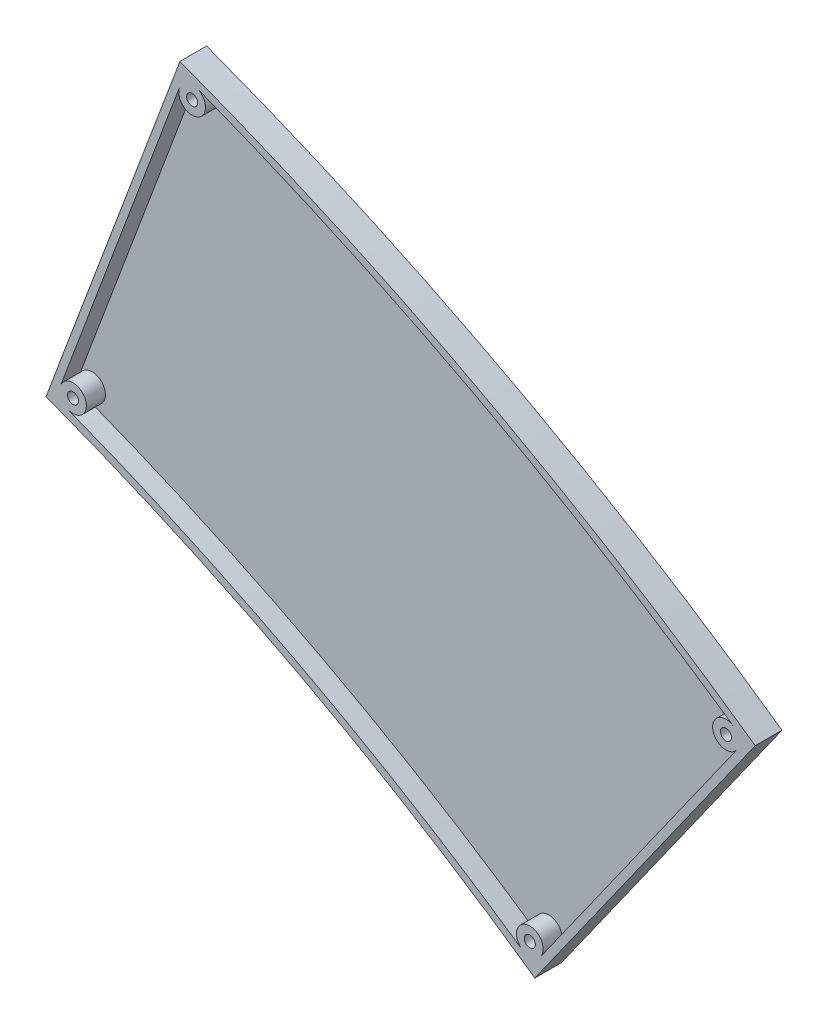
SolidWorks part; units mm, degrees
ref_plane "Front Plane" through (0, 0, 0) normal (0, 0, 1) x (1, 0, 0)
ref_plane "Top Plane" through (0, 0, 0) normal (0, 1, 0) x (1, 0, 0)
ref_plane "Right Plane" through (0, 0, 0) normal (1, 0, 0) x (0, 0, -1)
sketch "Sketch2" plane through (0, 0, 0) normal (0, 0, 1) x (1, 0, 0)
  line L0 (0, 0) -> (198.2974, 529.0587) construction
  line L1 (0, 0) -> (326.4209, 461.1664) construction
  line L2 (198.2974, 529.0587) -> (233.3943, 622.6975)
  line L3 (326.4209, 461.1664) -> (384.1945, 542.7887)
  arc A1 (326.4209, 461.1664) -> (198.2974, 529.0587) centre (0, 0) ccw
  arc A2 (384.1945, 542.7887) -> (233.3943, 622.6975) centre (0, 0) ccw
  dimension "D1" = 1330
  dimension "D2" = 100
  dimension "D3" = 145
extrude "Boss-Extrude1" add sketch "Sketch2" against normal blind 2
sketch "Sketch4" plane through (0, 0, 0) normal (0, 0, 1) x (1, 0, 0)
  line L0 (233.3943, 622.6975) -> (198.2974, 529.0587)
  line L1 (326.4209, 461.1664) -> (384.1945, 542.7887)
  arc A0 (198.2974, 529.0587) -> (326.4209, 461.1664) centre (0, 0) cw
  arc A1 (384.1945, 542.7887) -> (233.3943, 622.6975) centre (0, 0) ccw
extrude "Extrude-Thin1" add sketch "Sketch4" along normal blind 5 thin thin type one direction reverse wall 2
sketch "Sketch8" plane through (0, 0, 0) normal (0, 0, 1) x (1, 0, 0)
  line L0 (325.9418, 463.9514) -> (381.4048, 542.3093) construction
  line L1 (381.4048, 542.3093) -> (379.3712, 539.4363)
  line L3 (234.564, 620.1199) -> (233.3287, 616.8239)
  line L4 (202.0912, 533.4821) -> (200.8708, 530.2263)
  line L5 (327.9506, 466.7894) -> (325.9418, 463.9514)
  arc A0 (378.5126, 544.3319) -> (379.3712, 539.4363) centre (376.5144, 541.4583) ccw
  arc A1 (233.3287, 616.8239) -> (237.8617, 618.8625) centre (236.606, 615.5955) ccw
  arc A2 (325.9418, 463.9514) -> (200.8708, 530.2263) centre (0, 0) ccw construction
  arc A4 (381.4048, 542.3093) -> (234.564, 620.1199) centre (0, 0) ccw construction
  arc A5 (204.1086, 528.9884) -> (202.0912, 533.4821) centre (205.3685, 532.2537) ccw
  arc A6 (327.9506, 466.7894) -> (323.0994, 465.9354) centre (325.0939, 468.8115) ccw
  arc A7 (237.8617, 618.8625) -> (234.564, 620.1199) centre (0, 0) ccw
  arc A8 (381.4048, 542.3093) -> (378.5126, 544.3319) centre (0, 0) ccw
  arc A10 (325.9418, 463.9514) -> (323.0994, 465.9354) centre (0, 0) ccw
  arc A11 (204.1086, 528.9884) -> (200.8708, 530.2263) centre (0, 0) ccw
extrude "Boss-Extrude15" add sketch "Sketch8" along normal blind 5
sketch "Sketch14" plane through (0, 0, 5) normal (0, 0, 1) x (1, 0, 0)
  circle A0 centre (236.606, 615.5955) radius 3.5
  circle A1 centre (205.3685, 532.2537) radius 3.5
  circle A2 centre (325.0939, 468.8115) radius 3.5
  circle A3 centre (376.5144, 541.4583) radius 3.5
extrude "Cut-Extrude7" cut sketch "Sketch14" along normal blind 1.5 from surface starting at face at (286.767, 541.1741, -2)
sketch "Sketch15" plane through (0, 0, -0.5) normal (0, 0, -1) x (-1, 0, 0)
  circle A0 centre (-376.5144, 541.4583) radius 1.45
  circle A1 centre (-325.0939, 468.8115) radius 1.45
  circle A2 centre (-205.3685, 532.2537) radius 1.45
  circle A3 centre (-236.606, 615.5955) radius 1.45
extrude "Cut-Extrude8" cut sketch "Sketch15" against normal through all
